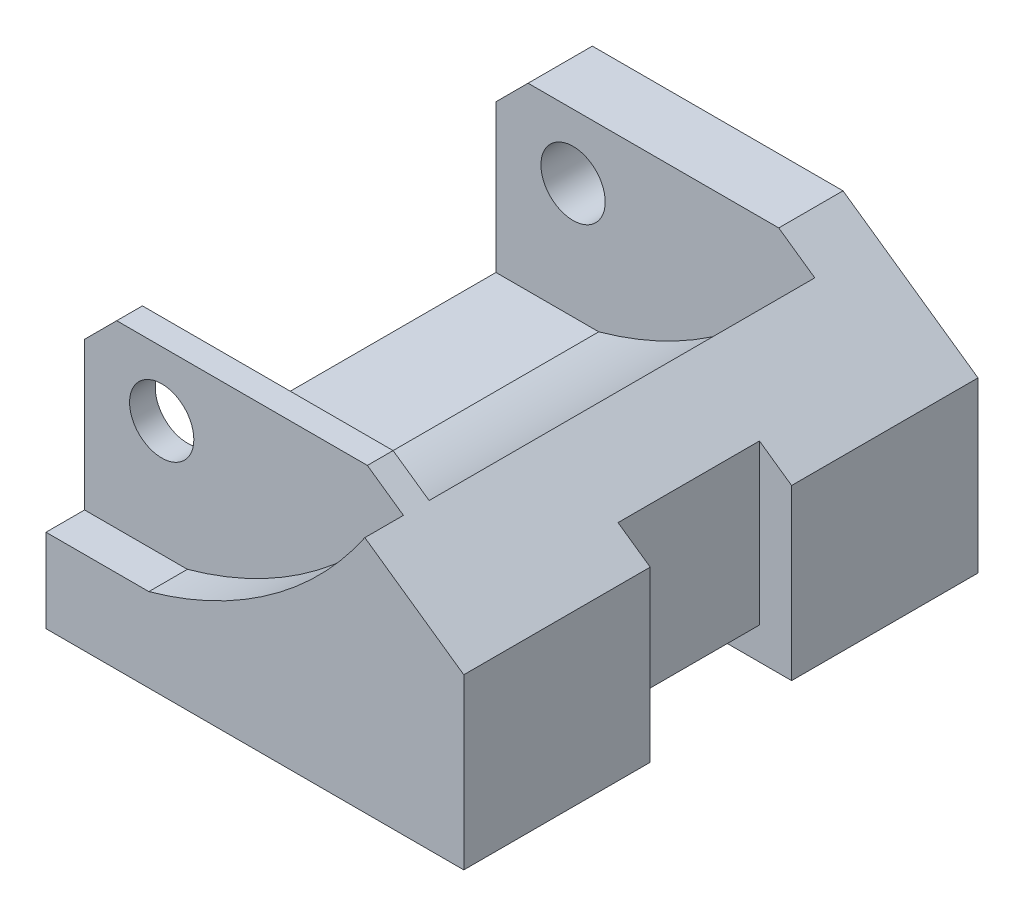
SolidWorks part; units mm, degrees
ref_plane "Front Plane" through (0, 0, 0) normal (0, 0, 1) x (1, 0, 0)
ref_plane "Top Plane" through (0, 0, 0) normal (0, 1, 0) x (1, 0, 0)
ref_plane "Right Plane" through (0, 0, 0) normal (1, 0, 0) x (0, 0, -1)
sketch "Sketch1" plane through (0, 0, 0) normal (0, 0, 1) x (1, 0, 0)
  line L0 (0, 0) -> (65, 0)
  line L1 (65, 0) -> (65, 26.2956)
  line L2 (65, 26.2956) -> (44, 41)
  line L3 (44, 41) -> (0, 41)
  line L5 (0, 41) -> (0, 0)
  line L6 (44, 41) -> (63.115, 41) construction
  circle A0 centre (12, 31) radius 5
  dimension "D2" = 10
  dimension "D1" = 65
  dimension "D3" = 12
  dimension "D4" = 10
  dimension "D5" = 21
  dimension "D6" = 35
  dimension "D7" = 41
extrude "Boss-Extrude1" add sketch "Sketch1" along normal mid plane 80
chamfer "Chamfer1" distance 5 angle 45 1 edges at (0, 41, 0)
sketch "Sketch3" plane through (0, 0, 0) normal (0, 0, 1) x (1, 0, 0)
  line L0 (0, 13) -> (16, 13)
  line L1 (0, 36) -> (0, 0) construction
  line L2 (65, 26.2956) -> (44, 41) construction
  line L3 (44, 41) -> (5, 41) construction
  line L4 (5, 41) -> (0, 36) construction
  line L6 (44, 41) -> (5, 41)
  line L7 (5, 41) -> (0, 36)
  line L8 (0, 36) -> (0, 13)
  line L9 (0, 13) -> (0, 70.8273) construction
  line L10 (49.606, 37.0746) -> (44, 41)
  circle A1 centre (12, 31) radius 5 construction
  circle A2 centre (12, 31) radius 5
  arc A3 (16, 13) -> (49.606, 37.0746) centre (0, 70.8273) ccw
  point P7 (0, 0)
  point P12 (0, 0)
  dimension "D2" = 60
  dimension "D1" = 16
  dimension "D3" = 28
extrude "Cut-Extrude1" cut sketch "Sketch3" against normal mid plane 60
extrude "Cut-Extrude2" cut sketch "Sketch3<2>" against normal blind 6 from surface starting at face at (29.8333, 24.0493, 40)
sketch "Sketch3<2>" plane through (0, 0, 0) normal (0, 0, 1) x (1, 0, 0) same geometry as "Sketch3"
sketch "Sketch5" plane through (65, 0, 0) normal (1, 0, 0) x (0, 0, -1)
  line L0 (0, 0) -> (0, 35.3084) construction
  line L1 (-11, 35.3084) -> (11, 35.3084)
  line L2 (-11, 35.3084) -> (-11, 0)
  line L3 (-40, 0) -> (40, 0) construction
  line L4 (11, 35.3084) -> (11, 0)
  line L5 (-11, 5) -> (11, 5)
  line L6 (-11, 0) -> (11, 0)
  point P6 (0, 35.3084)
  point P12 (11, 17.6542)
  point P13 (0, 0)
  point P14 (0, 35.3084)
  point P15 (0, 0)
  line M2 (40, 26.2956) -> (-40, 26.2956)
  line M4 (-40, 0) -> (40, 0)
  dimension "D1" = 22
  dimension "D2" = 5
extrude "Cut-Extrude3" cut sketch "Sketch5" against normal blind 5 contours L0 L4 L1 M2 | L0 L5 L4 M2 | L0 L1 L2 M2 | L5 L0 L2 M2 region at (65, 15.6478, 5.5) region at (65, 15.6478, -5.5) region at (65, 30.802, 5.5) region at (65, 30.802, -5.5)
extrude "Cut-Extrude4" cut sketch "Sketch5<4>" against normal through all contours L0 L6 L4 L5 | L0 L5 L2 M4 region at (65, 2.5, 5.5) region at (65, 2.5, -5.5)
sketch "Sketch5<4>" plane through (65, 0, 0) normal (1, 0, 0) x (0, 0, -1) same geometry as "Sketch5"
